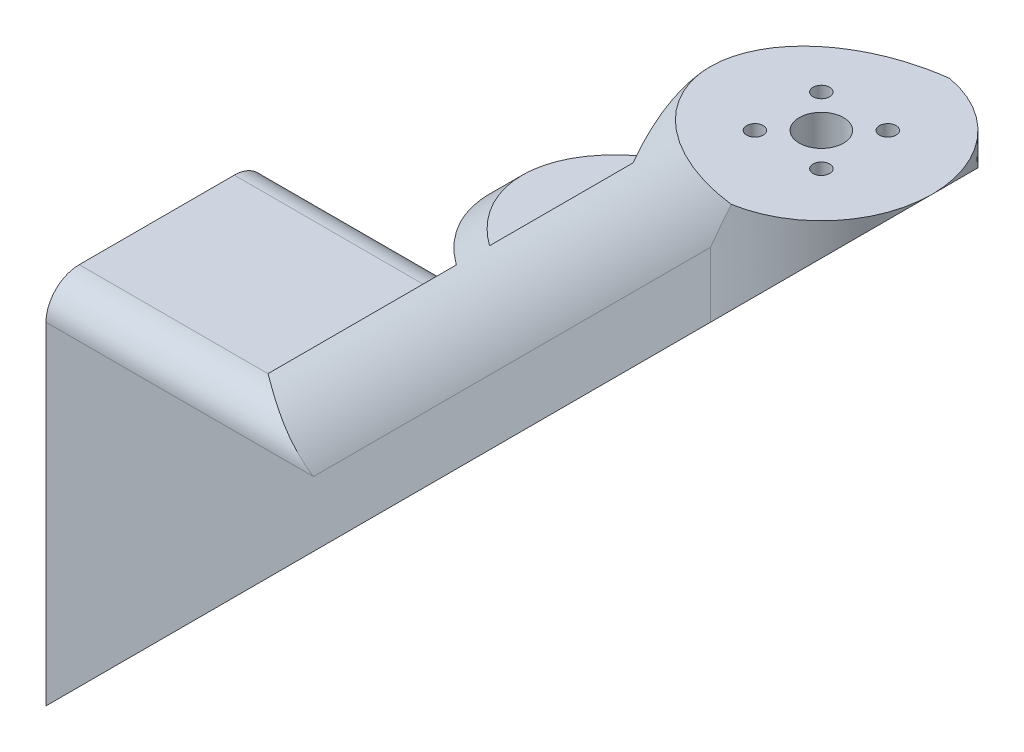
SolidWorks part; units mm, degrees
ref_plane "Front Plane" through (0, 0, 0) normal (0, 0, 1) x (1, 0, 0)
ref_plane "Top Plane" through (0, 0, 0) normal (0, 1, 0) x (1, 0, 0)
ref_plane "Right Plane" through (0, 0, 0) normal (1, 0, 0) x (0, 0, -1)
sketch "Sketch1" plane through (0, 0, 0) normal (0, 0, 1) x (1, 0, 0)
  line L0 (0, 0) -> (40, 0) construction
  line L1 (40, 0) -> (40, 150) construction
  line L2 (40, 150) -> (0, 150) construction
  line L3 (0, 150) -> (0, 80) construction
  line L4 (0, 80) -> (40, 80) construction
  line L5 (0, 80) -> (0, 70) construction
  line L6 (0, 70) -> (40, 70) construction
  line L7 (0, 70) -> (0, 0) construction
  line L8 (124.1123, 53.7532) -> (194.1123, 53.7532) construction
  line L9 (194.1123, 53.7532) -> (194.1123, 123.7532) construction
  line L10 (194.1123, 123.7532) -> (124.1123, 53.7532) construction
  line L11 (194.1123, 123.7532) -> (194.1123, 143.7532) construction
  line L12 (194.1123, 143.7532) -> (174.1123, 143.7532)
  line L13 (124.1123, 53.7532) -> (124.1123, 93.7532) construction
  line L15 (194.1123, 143.7532) -> (194.1123, 133.7532)
  line L16 (124.1123, 53.7532) -> (124.1123, 63.7532) construction
  line L17 (124.1123, 63.7532) -> (194.1123, 133.7532)
  line L18 (124.1123, 63.7532) -> (124.1123, 93.7532)
  line L19 (124.1123, 93.7532) -> (124.1123, 103.7532)
  line L20 (124.1123, 103.7532) -> (134.1123, 103.7532)
  line L22 (174.1123, 143.7532) -> (134.1123, 103.7532)
extrude "Boss-Extrude1" add sketch "Sketch1" along normal blind 20
sketch "Sketch2" plane through (124.1123, 0, 0) normal (-1, 0, 0) x (0, 0, 1)
  line L0 (0, 103.7532) -> (3, 103.7532) construction
  line L1 (20, 103.7532) -> (0, 103.7532) construction
  line L5 (17, 103.7532) -> (3, 103.7532)
  line L6 (3, 103.7532) -> (3, 123.7532)
  line L7 (3, 123.7532) -> (17, 123.7532)
  line L8 (17, 123.7532) -> (17, 103.7532)
  line L9 (3, 103.7532) -> (17, 103.7532)
  line M6 (20, 103.7532) -> (0, 103.7532)
extrude "Cut-Extrude1" cut sketch "Sketch2" against normal blind 100 contours L8 L7 L6 M6
sketch "Sketch3" plane through (124.1123, 0, 0) normal (-1, 0, 0) x (0, 0, 1)
  line L0 (3, 103.7532) -> (3, 98.7532) construction
  line L2 (17, 63.7532) -> (3, 63.7532)
  line L3 (20, 63.7532) -> (0, 63.7532) construction
  line L6 (3, 98.7532) -> (3, 63.7532)
  line L7 (3, 98.7532) -> (17, 98.7532)
  line L8 (17, 98.7532) -> (17, 63.7532)
extrude "Cut-Extrude2" cut sketch "Sketch3" along direction (1, 0, 0) on the side against the normal blind 100 from offset 3 offset against normal yes
sketch "Sketch5" plane through (194.1123, 0, 0) normal (1, 0, 0) x (0, 0, -1)
  line L0 (0, 143.7532) -> (-3, 143.7532) construction
  line L1 (-20, 143.7532) -> (0, 143.7532) construction
  line L2 (-3, 143.7532) -> (-3, 140.7532) construction
  line L3 (-3, 140.7532) -> (-3, 133.7532)
  line L4 (-20, 133.7532) -> (0, 133.7532) construction
  line L6 (-17, 133.7532) -> (-17, 140.7532)
  line L7 (-17, 140.7532) -> (-3, 140.7532)
  line L8 (-17, 133.7532) -> (-17, 116.7532)
  line L9 (-17, 116.7532) -> (-3, 116.7532)
  line L10 (-3, 116.7532) -> (-3, 133.7532)
extrude "Cut-Extrude3" cut sketch "Sketch5" against normal blind 14 from offset 3 offset against normal yes
sketch "Sketch8" plane through (0, 143.7532, 0) normal (0, 1, 0) x (1, 0, 0)
  line L0 (184.1123, 0) -> (184.1123, -10) construction
  line L1 (194.1123, 0) -> (174.1123, 0) construction
  line L2 (184.1123, -10) -> (187.1123, -10) construction
  line L3 (187.1123, -10) -> (187.1123, -13) construction
  line L4 (187.1123, -13) -> (187.1123, -7) construction
  line L5 (187.1123, -7) -> (181.1123, -7) construction
  line L6 (181.1123, -7) -> (181.1123, -13) construction
  line L7 (181.1123, -13) -> (187.1123, -13) construction
  circle A0 centre (187.1123, -7) radius 0.75
  circle A1 centre (187.1123, -13) radius 0.75
  circle A2 centre (181.1123, -13) radius 0.75
  circle A3 centre (181.1123, -7) radius 0.75
  circle A4 centre (184.1123, -10) radius 2
extrude "Cut-Extrude6" cut sketch "Sketch8" against normal blind 14
sketch "Sketch9" plane through (0, 0, 20) normal (0, 0, 1) x (1, 0, 0)
  line L0 (124.1123, 63.7532) -> (124.1123, 73.7532)
  line L1 (124.1123, 103.7532) -> (124.1123, 63.7532) construction
  line L2 (124.1123, 73.7532) -> (194.1123, 143.7532)
  line L3 (194.1123, 143.7532) -> (194.1123, 133.7532)
  line L4 (194.1123, 133.7532) -> (124.1123, 63.7532)
extrude "Cut-Extrude7" cut sketch "Sketch9" against normal blind 40
sketch "Sketch10" plane through (0, 0, 3) normal (0, 0, 1) x (1, 0, 0)
  line L0 (154.1123, 123.7532) -> (154.1123, 143.7532) construction
  line L1 (154.1123, 143.7532) -> (174.1123, 143.7532)
  line L2 (174.1123, 143.7532) -> (174.1123, 116.7532) construction
  line L3 (174.1123, 116.7532) -> (154.1123, 116.7532) construction
  line L4 (154.1123, 116.7532) -> (154.1123, 143.7532) construction
  line L5 (174.1123, 143.7532) -> (174.1123, 126.7532)
  line L6 (174.1123, 126.7532) -> (154.1123, 126.7532)
  line L7 (154.1123, 126.7532) -> (154.1123, 143.7532)
extrude "Cut-Extrude8" cut sketch "Sketch10" along normal blind 14
sketch "Sketch14" plane through (0, 0, 20) normal (0, 0, 1) x (1, 0, 0)
  line L0 (124.1123, 103.7532) -> (124.1123, 106.7532)
  line L1 (124.1123, 106.7532) -> (157.1123, 106.7532)
  line L2 (194.1123, 143.7532) -> (124.1123, 73.7532) construction
  line L3 (124.1123, 103.7532) -> (154.1123, 103.7532)
  line L4 (154.1123, 103.7532) -> (157.1123, 106.7532)
extrude "Boss-Extrude5" add sketch "Sketch14" against normal blind 20
sketch "Sketch15" plane through (0, 0, 17) normal (0, 0, -1) x (-1, 0, 0)
  line L0 (-127.1123, 98.7532) -> (-127.1123, 101.7532)
  line L1 (-127.1123, 98.7532) -> (-149.1123, 98.7532)
  line L2 (-149.1123, 98.7532) -> (-152.1123, 98.7532)
  line L3 (-152.1123, 98.7532) -> (-152.1123, 101.7532)
  line L4 (-152.1123, 101.7532) -> (-127.1123, 101.7532)
extrude "Cut-Extrude9" cut sketch "Sketch15" along normal blind 14
fillet "Fillet1" radius 10 2 edges at (155.6123, 125.2532, 0) (155.6123, 125.2532, 20)
fillet "Fillet2" radius 5 2 edges at (139.6123, 101.7532, 17) (139.6123, 101.7532, 3)
fillet "Fillet3" radius 3 2 edges at (137.6834, 106.7532, 0) (137.6834, 106.7532, 20)
sketch "Sketch20" plane through (0, 143.7532, 0) normal (0, 1, 0) x (1, 0, 0)
  line L0 (194.1123, -20) -> (194.1123, 0) construction
  line L1 (148.2544, 0) -> (188.2544, 0) construction
  line L2 (188.2544, -20) -> (148.2544, -20) construction
  line L7 (184.1123, 0) -> (184.1123, 5)
  line L8 (184.1123, 5) -> (199.1123, 5)
  line L9 (199.1123, 5) -> (199.1123, -25)
  line L10 (199.1123, -25) -> (184.1123, -25)
  line L11 (184.1123, -25) -> (184.1123, -20)
  ellipse E0 centre (184.1123, -10) end of major axis (194.1123, -10) minor radius 10 (184.1123, 0) -> (184.1123, -20) cw
  ellipse M6 centre (188.2544, -10) end of major axis (174.1123, -10) minor radius 10 (188.2544, 0) -> (174.1123, -10) ccw
  ellipse M7 centre (188.2544, -10) end of major axis (202.3966, -10) minor radius 10 (174.1123, -10) -> (188.2544, -20) ccw
  line M8 (188.2544, -20) -> (194.1123, -20)
  line M9 (194.1123, -20) -> (194.1123, 0)
  line M10 (194.1123, 0) -> (188.2544, 0)
extrude "Cut-Extrude11" cut sketch "Sketch20" against normal blind 14 contours E0 L11 L10 L9 L8 L7 M7 M6 M10 M9 M8 | E0 M9 M7 M8 | E0 M6 M9 M10
sketch "Sketch21" plane through (124.1123, 0, 0) normal (-1, 0, 0) x (0, 0, 1)
  line L0 (10, 106.7532) -> (10, 94.7532) construction
  line L1 (3, 106.7532) -> (17, 106.7532) construction
  line L2 (10, 94.7532) -> (10, 82.7532) construction
  circle A0 centre (10, 94.7532) radius 2.5
  circle A1 centre (10, 82.7532) radius 2.5
extrude "Cut-Extrude12" cut sketch "Sketch21" against normal blind 10 and the other way blind 1
